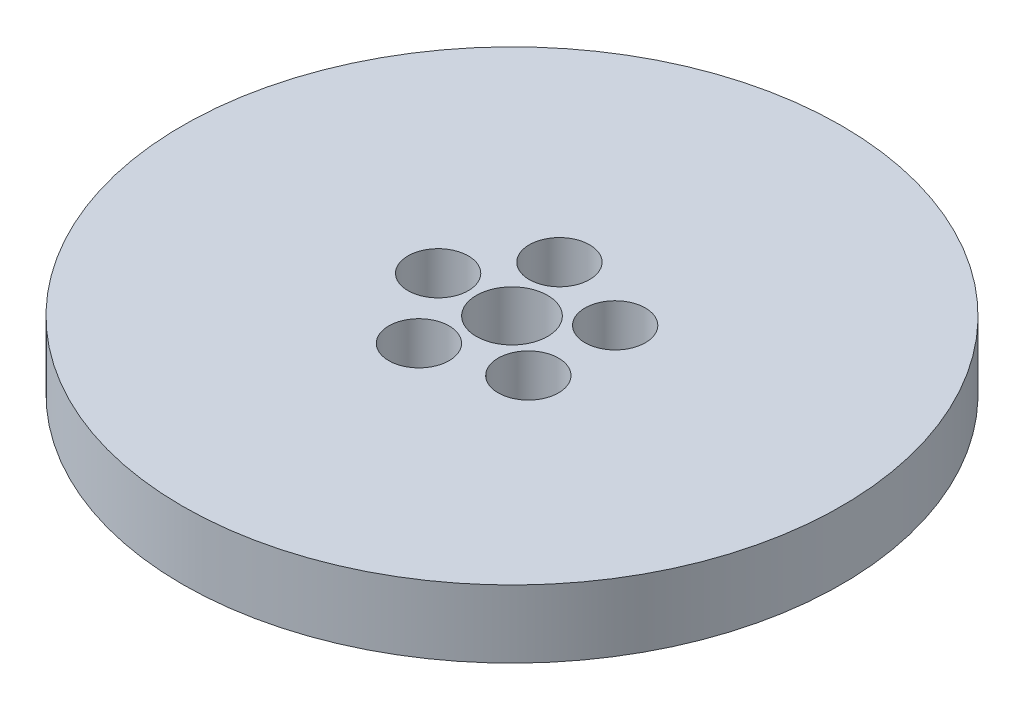
SolidWorks part; units mm, degrees
ref_plane "Front Plane" through (0, 0, 0) normal (0, 0, 1) x (1, 0, 0)
ref_plane "Top Plane" through (0, 0, 0) normal (0, 1, 0) x (1, 0, 0)
ref_plane "Right Plane" through (0, 0, 0) normal (1, 0, 0) x (0, 0, -1)
sketch "Sketch1" plane through (0, 0, 0) normal (0, 1, 0) x (1, 0, 0)
  circle A0 centre (0, 0) radius 92.5
  dimension "FLANGE_OD" = 185
extrude "Boss-Extrude1" add sketch "Sketch1" along normal blind 19
sketch "Sketch2" plane through (0, 0, 0) normal (0, 1, 0) x (1, 0, 0)
  circle A0 centre (0, 0) radius 10
  dimension "BORE_D" = 20
extrude "Cut-Extrude1" cut sketch "Sketch2" along normal through all
sketch "Sketch3" plane through (0, 19, 0) normal (0, 1, 0) x (1, 0, 0)
  circle A0 centre (0, 0) radius 20.7314 construction
  circle A1 centre (-20.7314, 0) radius 8.4707
  dimension "BOLT_D" = 16.9414
  dimension "BOLT_PCD" = 41.4628
extrude "Cut-Extrude2" cut sketch "Sketch3" against normal blind 12.5742
pattern_circular "CirPattern1" count 5 over 360 about axis through (0, 0, 0) along (0, 1, 0) of "Cut-Extrude2"
